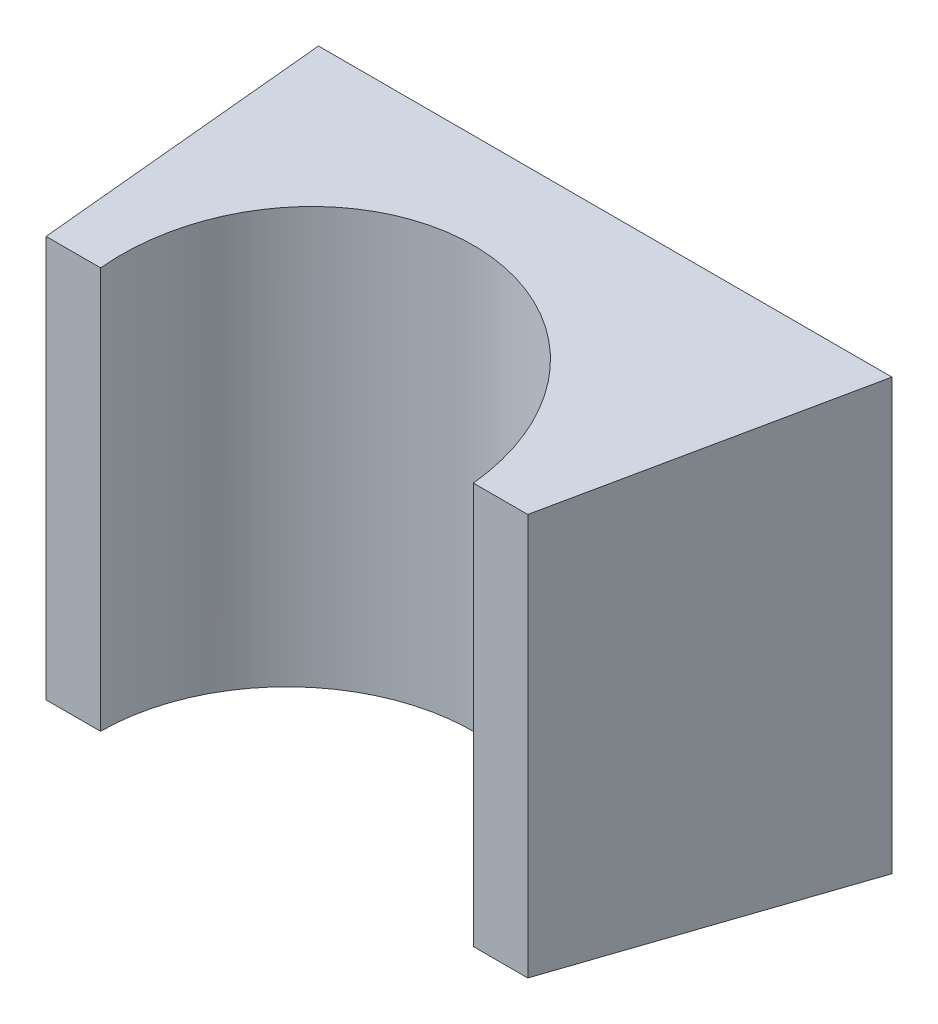
SolidWorks part; units mm, degrees
material "ABS"
ref_plane "Front Plane" through (0, 0, 0) normal (0, 0, 1) x (1, 0, 0)
ref_plane "Top Plane" through (0, 0, 0) normal (0, 1, 0) x (1, 0, 0)
ref_plane "Right Plane" through (0, 0, 0) normal (1, 0, 0) x (0, 0, -1)
sketch "Sketch1" plane through (0, 0, 0) normal (0, 0, 1) x (1, 0, 0)
  line L1 (-20, 25) -> (20, 25)
  line L2 (-20, 25) -> (-20, -5)
  line L3 (-20, -5) -> (20, -5)
  line L4 (20, 25) -> (20, -5)
  line L5 (-20, 25) -> (20, -5) construction
  line L6 (-20, -5) -> (20, 25) construction
  point P0 (0, 10)
  dimension "D1" = 40
  dimension "D2" = 30
  dimension "D3" = 10
extrude "Boss-Extrude1" add sketch "Sketch1" along normal blind 19
sketch "Sketch8" plane through (-20, 0, 0) normal (-1, 0, 0) x (0, 0, 1)
  line L0 (0, 25) -> (19, 23)
  line L1 (19, 25) -> (19, -5) construction
  line L2 (19, 23) -> (19, 25)
  line L3 (19, 25) -> (0, 25)
  dimension "D1" = 2
extrude "Cut-Extrude3" cut sketch "Sketch8" against normal up to surface (40 mm away) up to face at (20, 10, 9.5)
sketch "Sketch2" plane through (0, -5, 0) normal (0, -1, 0) x (1, 0, 0)
  line L0 (-20, 19) -> (20, 19) construction
  line L1 (-20, 0) -> (20, 0) construction
  line L2 (13.6, 19) -> (20, 0)
  line L3 (13.6, 19) -> (20, 19)
  line L4 (20, 19) -> (20, 0) construction
  line L5 (20, 19) -> (20, 0)
  circle A0 centre (-3.2, 19) radius 13
  point P4 (0, 0)
  point P11 (-16.2, 19)
  point P16 (-20, 19)
  point P17 (9.8, 19)
  dimension "D1" = 26
  dimension "D2" = 3.2
  dimension "D3" = 3.8
  dimension "D4" = 3.8
extrude "Cut-Extrude1" cut sketch "Sketch2" against normal up to next
equation "\"D4@Sketch2\"=\"D3@Sketch2\""
